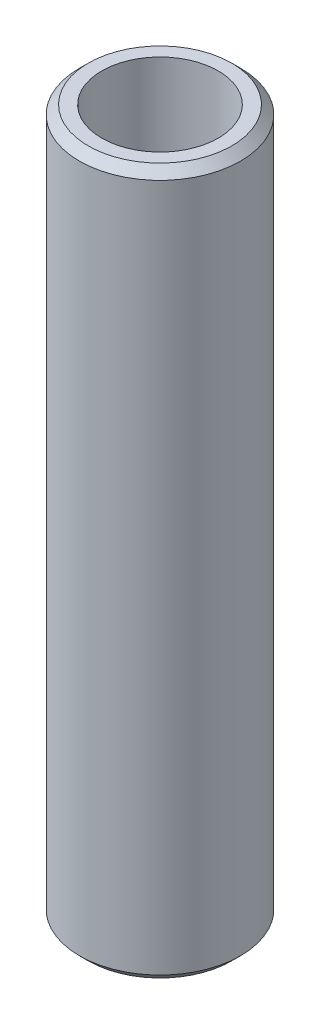
SolidWorks part; units mm, degrees
ref_plane "Front Plane" through (0, 0, 0) normal (0, 0, 1) x (1, 0, 0)
ref_plane "Top Plane" through (0, 0, 0) normal (0, 1, 0) x (1, 0, 0)
ref_plane "Right Plane" through (0, 0, 0) normal (1, 0, 0) x (0, 0, -1)
sketch "Sketch1" plane through (0, 0, 0) normal (0, 1, 0) x (1, 0, 0)
  circle A0 centre (0, 0) radius 55
  dimension "SHAFT_OD" = 110
extrude "Boss-Extrude1" add sketch "Sketch1" along normal blind 481.9839
sketch "Sketch2" plane through (0, 0, 0) normal (0, 1, 0) x (1, 0, 0)
  circle A0 centre (0, 0) radius 39.7928
  dimension "BORE_D" = 79.5856
extrude "Cut-Extrude1" cut sketch "Sketch2" along normal through all
chamfer "Chamfer1" distance 5.996 angle 45 2 edges at (0, 481.9839, 55) (0, 0, 55)
